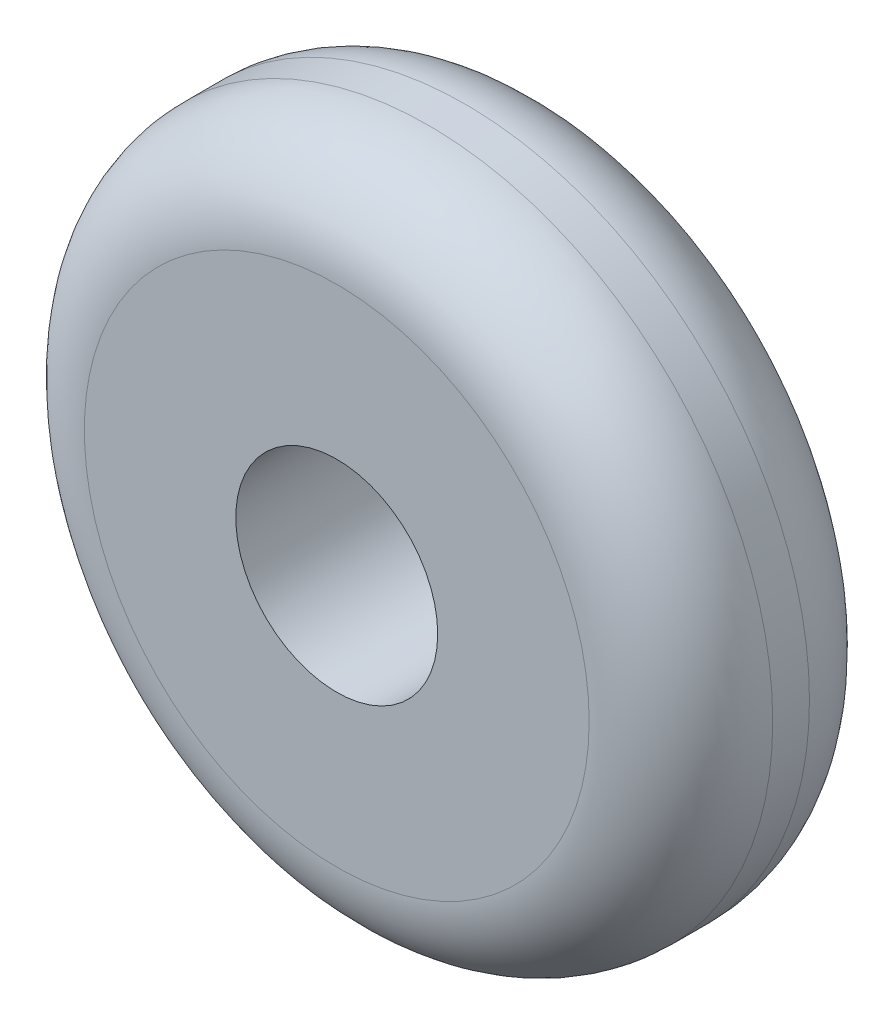
SolidWorks part; units mm, degrees
ref_plane "前视基准面" through (0, 0, 0) normal (0, 0, 1) x (1, 0, 0)
ref_plane "上视基准面" through (0, 0, 0) normal (0, 1, 0) x (1, 0, 0)
ref_plane "右视基准面" through (0, 0, 0) normal (1, 0, 0) x (0, 0, -1)
other "Configuration Table"
sketch "草图1" plane through (0, 0, 0) normal (0, 0, 1) x (1, 0, 0)
  circle A0 centre (0, 0) radius 37.5
  circle A1 centre (0, 0) radius 11
  dimension "D1" = 75
extrude "凸台-拉伸1" add sketch "草图1" along normal blind 24
fillet "圆角1" radius 10 2 edges at (37.5, 0, 0) (37.5, 0, 24)
ref_plane "基准面1" through (0, 0, 12) normal (0, 0, 1) x (1, 0, 0)
